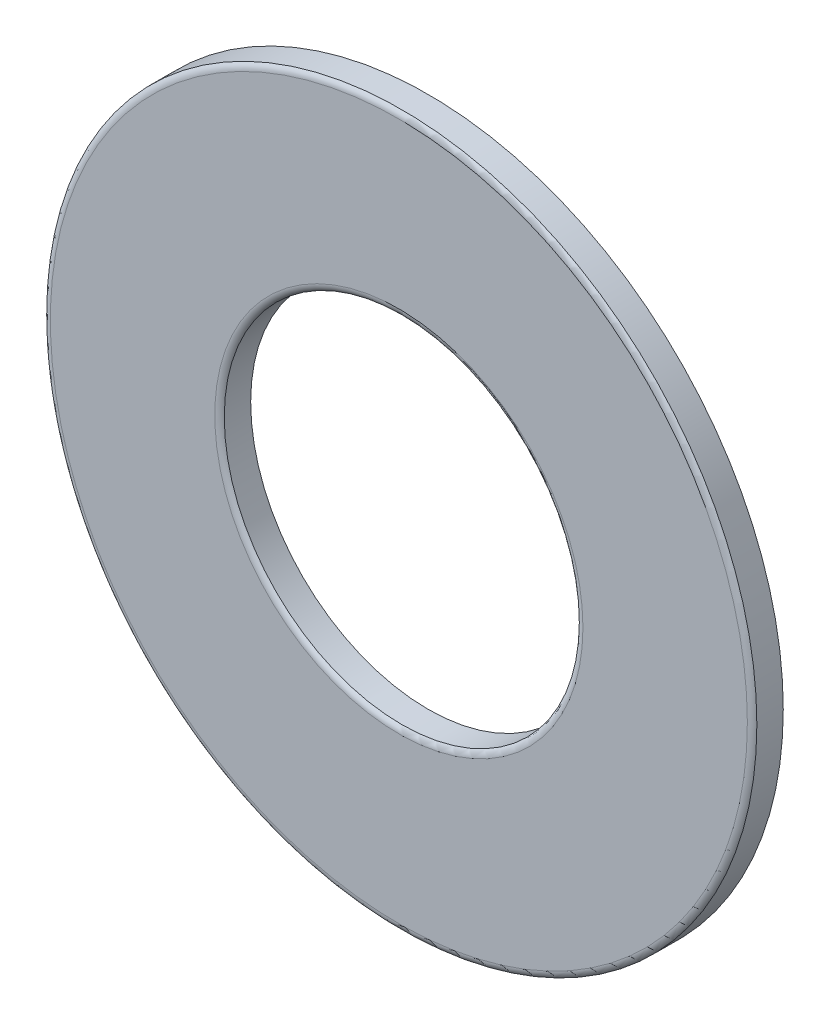
SolidWorks part; units mm, degrees
ref_plane "Front Plane" through (0, 0, 0) normal (0, 0, 1) x (1, 0, 0)
ref_plane "Top Plane" through (0, 0, 0) normal (0, 1, 0) x (1, 0, 0)
ref_plane "Right Plane" through (0, 0, 0) normal (1, 0, 0) x (0, 0, -1)
sketch "Sketch1" plane through (0, 0, 0) normal (0, 0, 1) x (1, 0, 0)
  circle A0 centre (0, 0) radius 19.05
  circle A1 centre (0, 0) radius 9.525
  point P4 (9.525, 0)
  dimension "ID" = 19.05
  dimension "OD" = 38.1
sketch "Sketch2" plane through (0, 0, 0) normal (1, 0, 0) x (0, 0, -1)
  line L0 (-0.7874, 19.05) -> (0.7874, 19.05)
  line L1 (0, 19.05) -> (0, 17.4752) construction
  point P2 (-0.8763, 19.05)
  point P3 (0, 19.05)
  point P4 (0.8763, 19.05)
  point P8 (-0.6985, 19.05)
  point P13 (0.6985, 19.05)
  dimension "Thickness Range" = 1.5748
  dimension "Thickness Range Max" = 1.7526
  dimension "Thickness Range Min" = 1.397
sketch "Sketch3" plane through (0, 0, 0) normal (0, 0, 1) x (1, 0, 0)
  circle A0 centre (0, 0) radius 9.525 construction
  circle A1 centre (0, 0) radius 19.05 construction
  circle A2 centre (0, 0) radius 9.525
  circle A3 centre (0, 0) radius 19.05
extrude "Boss-Extrude1" add sketch "Sketch3" along normal up to vertex (0.7874 mm away) from vertex at -0.7874 starting at point (0, 19.05, -0.7874)
chamfer "Chamfer1" distance 0.1575 angle 30 2 edges at (19.05, 0, 0.7874) (9.525, 0, 0.7874)
fillet "Fillet1" radius 0.4724 2 edges at (9.6159, 0, 0.7874) (18.9591, 0, 0.7874)
equation "\"D1@Fillet1\"=\"D1@Chamfer1\"*3"
equation "\"D1@Chamfer1\"=\"Thickness Range@Sketch2\"*.1"
